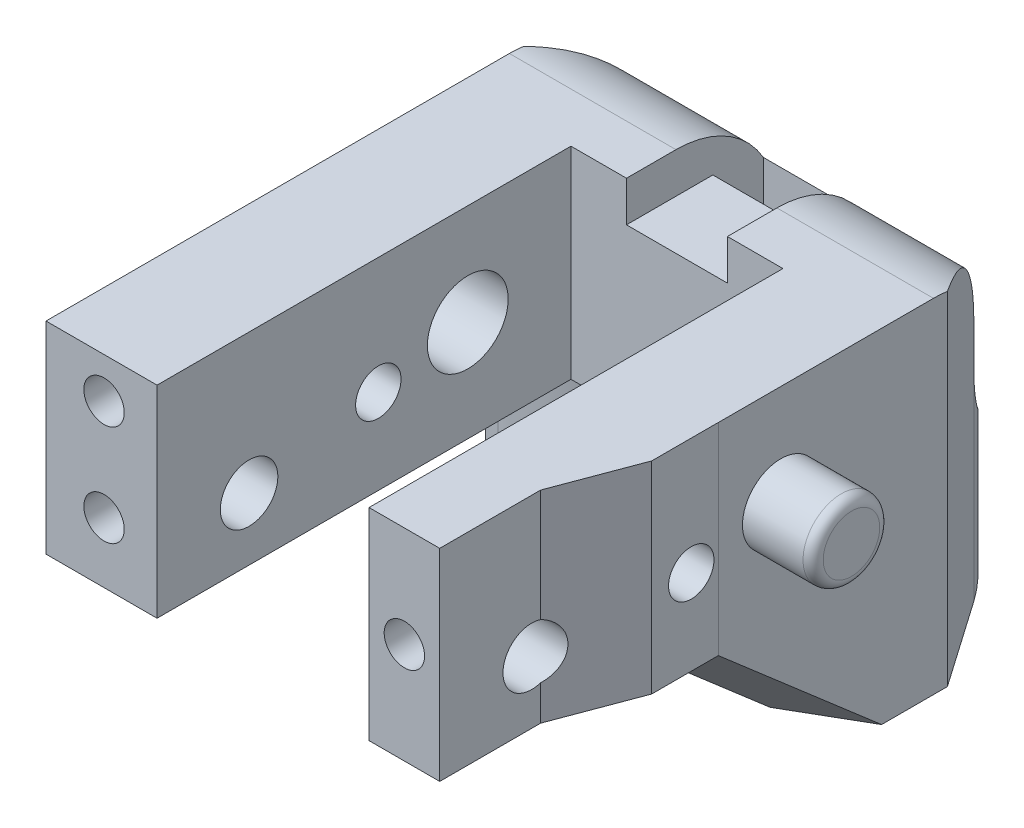
SolidWorks part; units mm, degrees
material "ABS"
ref_plane "Front Plane" through (0, 0, 0) normal (0, 0, 1) x (1, 0, 0)
ref_plane "Top Plane" through (0, 0, 0) normal (0, 1, 0) x (1, 0, 0)
ref_plane "Right Plane" through (0, 0, 0) normal (1, 0, 0) x (0, 0, -1)
sketch "Sketch1" plane through (0, 0, 0) normal (0, 1, 0) x (1, 0, 0)
  line L0 (-15.5, -37) -> (-10, -37)
  line L2 (-15.5, -37) -> (-15.5, 10)
  line L3 (-15.5, 10) -> (21, 10)
  line L4 (21, -19) -> (21, 10)
  line L5 (-10, -37) -> (-10, 4)
  line L6 (-10, 4) -> (11, 4)
  line L7 (11, 4) -> (11, -37)
  line L9 (21, -19) -> (18, -27)
  line L10 (18, -27) -> (18, -37)
  line L11 (11, -37) -> (18, -37)
  point P0 (0, 0)
  dimension "D1" = 36.5
  dimension "D2" = 7
  dimension "D3" = 21
  dimension "D4" = 10
  dimension "D5" = 21
  dimension "D6" = 41
  dimension "D7" = 47
  dimension "D8" = 8
  dimension "D9" = 5.5
  dimension "D10" = 10
extrude "Boss-Extrude1" add sketch "Sketch1" along normal blind 20
sketch "Sketch6" plane through (-15.5, 0, 0) normal (-1, 0, 0) x (0, 0, 1)
  line L1 (15, 0) -> (-10, 0)
  line L2 (15, 0) -> (15, 20)
  line L3 (15, 20) -> (-10, 20)
  line L4 (-10, 0) -> (-10, 20)
  line L5 (-10, 20) -> (-10, 0) construction
  line L7 (-10, 0) -> (37, 0) construction
  line L8 (-10, 20) -> (37, 20) construction
  dimension "D3" = 25
extrude "Boss-Extrude5" add sketch "Sketch6" along normal blind 5.5
sketch "Sketch20" plane through (0, 20, 0) normal (0, 1, 0) x (1, 0, 0)
  line L4 (-21, 6.5542) -> (14, 6.5542)
  line L11 (21.0063, -12.4007) -> (21.0063, 10.2821)
  line L12 (21.0063, 10.2821) -> (15.0032, 18.9016)
  line L13 (15.0032, 18.9016) -> (-14.9968, 18.9016)
  line L14 (-14.9968, 18.9016) -> (-21, 10.2821)
  line L15 (-21, 10) -> (-21, -15) construction
  line L16 (-21, 10.2821) -> (-21, 6.5542)
  line L18 (14, 6.5542) -> (14, -16.4458)
  line L20 (14, -16.4458) -> (21.0063, -12.4007)
  dimension "D2" = 23
  dimension "D4" = 30
  dimension "D8" = 35
  dimension "D9" = 60
  dimension "D1" = 6.0032
  dimension "D3" = 6.0032
  dimension "D5" = 8.6195
  dimension "D6" = 8.6195
  dimension "D7" = 3.7279
extrude "Boss-Extrude11" add sketch "Sketch20" along normal blind 14 and the other way up to surface (20 mm away) other way up to face at (0.5833, 0, 16.3333)
sketch "Sketch4" plane through (0, 20, 0) normal (0, 1, 0) x (1, 0, 0)
  line L2 (-10, 4) -> (11, 4) construction
  line L4 (-10, -37) -> (-10, 4) construction
  circle A6 centre (-4.375, 8) radius 2
  circle A7 centre (5.375, 8) radius 2
  dimension "D1" = 4
  dimension "D2" = 4
  dimension "D3" = 9.75
  dimension "D4" = 5.625
extrude "Cut-Extrude1" cut sketch "Sketch4" against normal blind 10
sketch "Sketch24" plane through (0, 34, 0) normal (0, 1, 0) x (1, 0, 0)
  line L0 (21.0063, 10.2821) -> (15.0032, 18.9016) construction
  line L1 (-14.9968, 18.9016) -> (-14.4209, 19.7285)
  line L2 (-21, 10.2821) -> (-21, 6.5542) construction
  line L3 (-14.9968, 18.9016) -> (-21, 10.2821) construction
  line L4 (21.0063, 10.2821) -> (15.0032, 18.9016)
  line L6 (-21, 10.2821) -> (-21, 6.5542)
  line L7 (-14.9968, 18.9016) -> (-21, 10.2821)
  line L11 (-21, 6.5542) -> (14, 6.5542) construction
  line L14 (-21, 6.5542) -> (21.0063, 6.5542)
  line L16 (21.0063, 10.2821) -> (21.0063, 6.5542)
  line L17 (21.0063, -12.4007) -> (21.0063, 10.2821) construction
  arc A3 (8.6131, 24.6437) -> (-14.4209, 19.7285) centre (-0.0555, 8.8374) ccw
  arc A4 (8.6131, 24.6437) -> (15.0032, 18.9016) centre (-0.4313, 8.152) cw
  dimension "D3" = 18.0273
  dimension "D4" = 18.8089
  dimension "D1" = 0.5759
  dimension "D2" = 1.0077
extrude "Boss-Extrude13" add sketch "Sketch24" against normal blind 12
fillet "Fillet11" radius 7.95 1 edges at (0.0032, 22, -18.9016)
sketch "Sketch22" plane through (0, 34, 0) normal (0, 1, 0) x (1, 0, 0)
  line L2 (-21, 10.2821) -> (-21, 6.5542) construction
  line L3 (-21, 6.5542) -> (14, 6.5542) construction
  circle A0 centre (-14.7203, 13.3514) radius 2
  circle A1 centre (-3.0673, 22.5813) radius 2
  dimension "D1" = 4
  dimension "D2" = 6.2797
  dimension "D3" = 6.7972
  dimension "D4" = 17.9327
  dimension "D5" = 16.0271
extrude "Cut-Extrude6" cut sketch "Sketch22" against normal blind 10
chamfer "Chamfer1" distance 14 angle 45 1 edges at (17.5032, 34, 14.4233)
sketch "Sketch26" plane through (-21, 0, 0) normal (-1, 0, 0) x (0, 0, 1)
  line L0 (15, 0) -> (37, 0)
  line L2 (37, 0) -> (37, 20)
  line L3 (37, 20) -> (15, 20)
  line L4 (15, 0) -> (15, 20) construction
  line L5 (15, 20) -> (15, 0)
extrude "Boss-Extrude14" add sketch "Sketch26" against normal up to surface (11 mm away) up to face at (-10, 10, 16.5)
sketch "Sketch25" plane through (-21, 0, 0) normal (-1, 0, 0) x (0, 0, 1)
  line L0 (11.8689, 14.9312) -> (31.15, 18.331)
  line L1 (13.2147, 7.2989) -> (32.4958, 10.6987)
  line L2 (32.4958, 10.6987) -> (31.15, 18.331) construction
  line L3 (6.2179, 10) -> (31.8229, 14.5149) construction
  line L4 (-10.2821, 0) -> (37, 0) construction
  line L5 (6.2179, 10) -> (6.2179, 38.8588) construction
  line L7 (-10.2821, 34) -> (-10.2821, 0) construction
  arc A1 (11.8689, 14.9312) -> (13.2147, 7.2989) centre (6.2179, 10) ccw
  arc A3 (31.15, 18.331) -> (32.4958, 10.6987) centre (31.8229, 14.5149) cw
  dimension "D2" = 7.75
  dimension "D1" = 7.5
  dimension "D4" = 7.75
  dimension "D3" = 26
  dimension "D5" = 80
  dimension "D7" = 10
  dimension "D6" = 16.5
  dimension "D8" = 3.875
extrude "Cut-Extrude7" cut sketch "Sketch25" against normal blind 2.5
sketch "Sketch27" plane through (-18.5, 0, 0) normal (-1, 0, 0) x (0, 0, 1)
  line L0 (6.2179, 10) -> (31.8229, 14.5149) construction
  circle A0 centre (6.2179, 10) radius 4
  circle A1 centre (15.0812, 11.5628) radius 1.15
  circle A4 centre (27.8837, 13.8203) radius 1.6
  dimension "D1" = 8
  dimension "D3" = 2.3
  dimension "D4" = 3.2
  dimension "D2" = 9
  dimension "D5" = 4
extrude "Cut-Extrude8" cut sketch "Sketch27" against normal up to next
sketch "Sketch28" plane through (-21, 0, 0) normal (-1, 0, 0) x (0, 0, 1)
  line L4 (-0.0283, 0.7779) -> (-3.1977, 15.9504)
  line L6 (13.3704, 7.7433) -> (11.8689, 14.9312) construction
  line L10 (-3.1977, 15.9504) -> (10.5064, 18.8131)
  line L11 (10.5064, 18.8131) -> (17.2487, 15.8798)
  line L13 (31.15, 18.331) -> (11.8689, 14.9312) construction
  line L14 (17.2487, 15.8798) -> (18.6801, 9.0277)
  line L16 (18.6801, 9.0277) -> (13.6759, 3.6406)
  line L17 (13.6759, 3.6406) -> (-0.0283, 0.7779)
  arc A0 (11.8689, 14.9312) -> (13.2147, 7.2989) centre (6.2179, 10) ccw construction
  circle A1 centre (6.2179, 10) radius 4 construction
  dimension "D1" = 15.5
  dimension "D2" = 7.75
  dimension "D3" = 8
  dimension "D4" = 14
  dimension "D5" = 14
  dimension "D6" = 6
  dimension "D7" = 7
extrude "Cut-Extrude9" cut sketch "Sketch28" against normal blind 2.5
sketch "Sketch31" plane through (-18.5, 0, 0) normal (-1, 0, 0) x (0, 0, 1)
  circle A0 centre (6.2179, 10) radius 4
  circle A1 centre (6.2179, 10) radius 1.65
  circle A2 centre (6.2179, 10) radius 4 construction
  dimension "D2" = 3.3
extrude "Boss-Extrude15" add sketch "Sketch31" along normal blind 1 and the other way blind 2
sketch "Sketch32" plane through (-10, 0, 0) normal (1, 0, 0) x (0, 0, -1)
  circle A0 centre (-27.8837, 13.8203) radius 2.85
  circle A3 centre (-15.0812, 11.5628) radius 2.25
  dimension "D1" = 5.7
  dimension "D2" = 4.5
extrude "Cut-Extrude12" cut sketch "Sketch32" against normal blind 7 and the other way up to next
sketch "Sketch33" plane through (21.0063, 0, 0) normal (1, 0, 0) x (0, 0, -1)
  circle A0 centre (-6.2179, 10) radius 3.8
  circle A1 centre (-6.2179, 10) radius 1.65 construction
  dimension "D1" = 7.6
extrude "Boss-Extrude17" add sketch "Sketch33" along normal blind 7
fillet "Fillet17" radius 1 1 edges at (28.0063, 10, 2.4179)
sketch "Sketch35" plane through (0, 34, 0) normal (0, 1, 0) x (1, 0, 0)
  line L0 (-21, 6.5542) -> (14, 6.5542) construction
  line L1 (-19.8, 6.5542) -> (14, 6.5542)
  line L3 (-9.8027, 12.5542) -> (14, 12.5542)
  line L4 (14, 6.5542) -> (14, 12.5542)
  line L7 (14, 6.5542) -> (14, -0.28) construction
  arc A0 (-19.8, 6.5542) -> (-12.285, 9.9568) centre (-19.8, 16.5542) ccw
  arc A1 (-12.285, 9.9568) -> (-9.8027, 12.5542) centre (19.6614, -18.0889) cw
  dimension "D3" = 42.5104
  dimension "D4" = 10
  dimension "D5" = 8.2494
  dimension "D1" = 23.8027
  dimension "D2" = 6
  dimension "D6" = 9.9972
extrude "Cut-Extrude13" cut sketch "Sketch35" against normal up to surface (14 mm away) up to face at (4.25, 20, 11.0396)
sketch "Sketch36" plane through (0, 0, 37) normal (0, 0, 1) x (1, 0, 0)
  line L0 (11, 20) -> (11, 0) construction
  line L1 (11, 20) -> (18, 20) construction
  line L2 (-21, 0) -> (-21, 20) construction
  line L6 (-21, 20) -> (-10, 20) construction
  circle A0 centre (-15.25, 14) radius 2
  circle A1 centre (14.5, 10) radius 2
  circle A2 centre (-15.25, 4) radius 2
  dimension "D3" = 4
  dimension "D1" = 5.75
  dimension "D2" = 3.5
  dimension "D4" = 10
  dimension "D5" = 6
  dimension "D6" = 5.75
  dimension "D7" = 10
extrude "Cut-Extrude14" cut sketch "Sketch36" against normal blind 10
fillet "Fillet18" radius 10 1 edges at (0.0032, 0, -18.9016)
sketch "Sketch37" plane through (21, 0, 0) normal (1, 0, 0) x (0, 0, -1)
  line L0 (-6.2179, 10) -> (6.304, 10) construction
  line L1 (4, 20) -> (4, 0) construction
  line L2 (-1.7179, 13) -> (4, 13)
  line L3 (-1.7179, 13) -> (-1.7179, 7)
  line L4 (-1.7179, 7) -> (4, 7)
  line L5 (4, 13) -> (4, 7)
  point P7 (0.043, 10)
  dimension "D1" = 6
  dimension "D2" = 3
  dimension "D4" = 4.5
extrude "Cut-Extrude16" cut sketch "Sketch37" against normal up to next
chamfer "Chamfer2" distance 7 angle 45 1 edges at (11, 10, 1.7179)
sketch "Sketch38" plane through (0, 0, 0) normal (0, -1, 0) x (1, 0, 0)
  line L0 (-10, -4) -> (11, -4) construction
  line L1 (-4.5, -4) -> (5.5, -4)
  line L2 (-4.5, -4) -> (-4.5, -24)
  line L3 (-4.5, -24) -> (5.5, -24)
  line L4 (5.5, -4) -> (5.5, -24)
  line L5 (-10, 37) -> (-10, -4) construction
  dimension "D1" = 10
  dimension "D2" = 5.5
  dimension "D3" = 20
extrude "Cut-Extrude17" cut sketch "Sketch38" against normal blind 4
sketch "Sketch39" plane through (0, 34, 0) normal (0, 1, 0) x (1, 0, 0)
  line L0 (14, 12.5542) -> (-9.8027, 12.5542) construction
  line L1 (-4.5, 12.5542) -> (5.5, 12.5542)
  line L2 (-4.5, 12.5542) -> (-4.5, 17.5542)
  line L3 (-4.5, 17.5542) -> (5.5, 17.5542)
  line L4 (5.5, 12.5542) -> (5.5, 17.5542)
  line L5 (5.5, 16.9016) -> (5.5, 4) construction
  line L6 (-4.5, 4) -> (-4.5, 16.9016) construction
  dimension "D1" = 5
extrude "Cut-Extrude19" cut sketch "Sketch39" against normal up to next
ref_plane "Plane1" through (0, -10, 0) normal (0, -1, 0) x (-1, 0, 0)
mirror "Mirror1" about plane through (0, -10, 0) normal (0, -1, 0) of bodies 140
sketch "Sketch40" plane through (0, 0, -18.9016) normal (0, 0, -1) x (-1, 0, 0)
  line L1 (30.516, -2.8705) -> (-40.4997, -2.8705)
  line L2 (30.516, -2.8705) -> (30.516, 39.4965)
  line L3 (30.516, 39.4965) -> (-40.4997, 39.4965)
  line L4 (-40.4997, -2.8705) -> (-40.4997, 39.4965)
extrude "Cut-Extrude20" cut sketch "Sketch40" against normal through all both and the other way through all
equation "\"D4@Sketch4\"=(21-\"D3@Sketch4\")/2"
equation "\"D2@Sketch37\"=\"D1@Sketch37\"/2"
equation "\"D3@Sketch20\"=\"D1@Sketch20\""
equation "\"D6@Sketch20\"=\"D5@Sketch20\""
equation "\"D5@Sketch28\"=\"D4@Sketch28\""
equation "\"D2@Sketch25\"=\"D4@Sketch25\""
equation "\"D8@Sketch25\"=\"D4@Sketch25\"/2"
